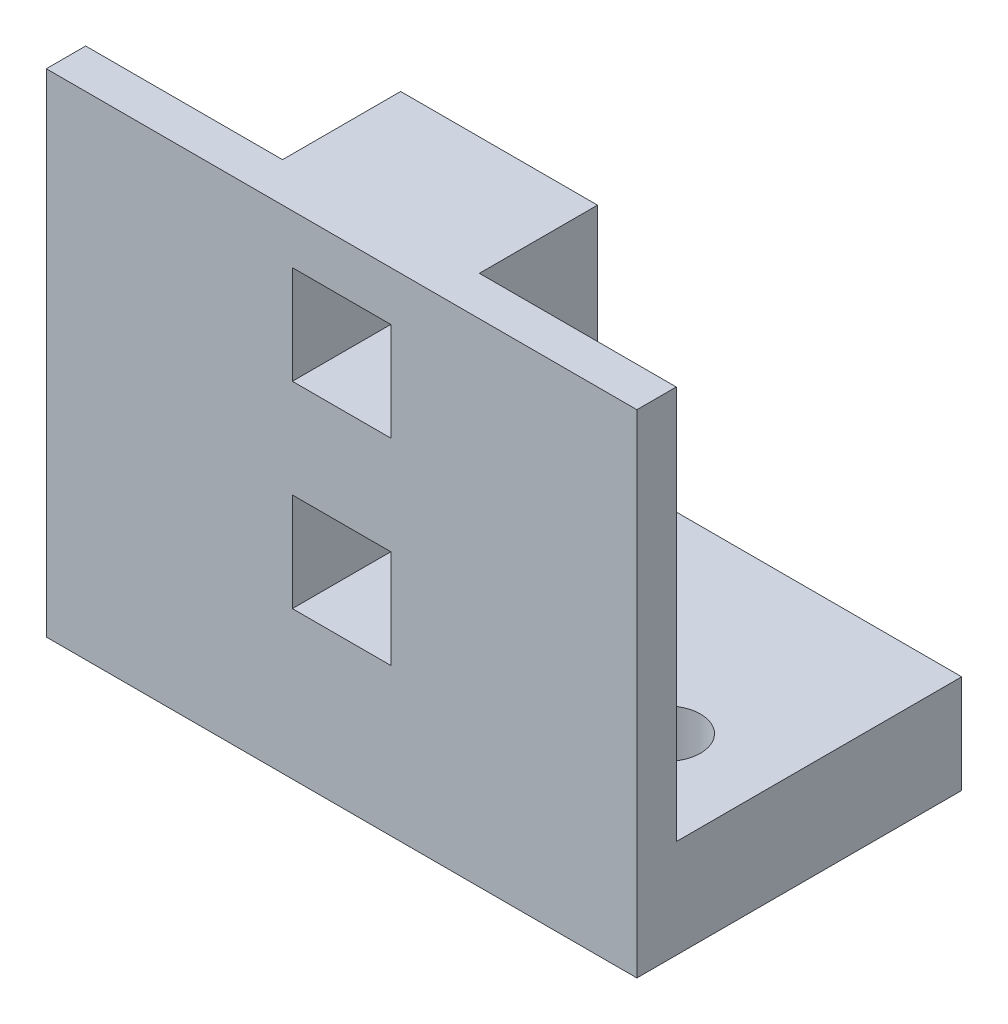
SolidWorks part; units mm, degrees
ref_plane "Front Plane" through (0, 0, 0) normal (0, 0, 1) x (1, 0, 0)
ref_plane "Top Plane" through (0, 0, 0) normal (0, 1, 0) x (1, 0, 0)
ref_plane "Right Plane" through (0, 0, 0) normal (1, 0, 0) x (0, 0, -1)
sketch "Sketch1" plane through (0, 0, 0) normal (0, 1, 0) x (1, 0, 0)
  line L1 (-15, 8.25) -> (15, 8.25)
  line L2 (-15, 8.25) -> (-15, -8.25)
  line L3 (-15, -8.25) -> (15, -8.25)
  line L4 (15, 8.25) -> (15, -8.25)
  line L5 (-15, 8.25) -> (15, -8.25) construction
  line L6 (-15, -8.25) -> (15, 8.25) construction
  circle A0 centre (-10, -1.75) radius 1.6514
  circle A1 centre (10, -1.75) radius 1.7283
  point P0 (0, 0)
  dimension "D3" = 10
  dimension "D4" = 10
  dimension "D5" = 5
  dimension "D1" = 16.5
  dimension "D2" = 30
  dimension "D6" = 5
extrude "Boss-Extrude1" add sketch "Sketch1" along normal blind 5
sketch "Sketch2" plane through (0, 0, 8.25) normal (0, 0, 1) x (1, 0, 0)
  line L1 (-15, 5) -> (15, 5)
  line L2 (-15, 5) -> (-15, 25)
  line L3 (-15, 25) -> (15, 25)
  line L4 (15, 5) -> (15, 25)
  dimension "D1" = 20
extrude "Boss-Extrude2" add sketch "Sketch2" against normal blind 2
sketch "Sketch3" plane through (0, 0, 6.25) normal (0, 0, -1) x (-1, 0, 0)
  line L0 (15, 5) -> (-15, 5) construction
  line L9 (-2.5, 7.5) -> (2.5, 7.5)
  line L10 (-2.5, 7.5) -> (-2.5, 12.5)
  line L11 (-2.5, 12.5) -> (2.5, 12.5)
  line L12 (2.5, 7.5) -> (2.5, 12.5)
  line L13 (-2.5, 17.5) -> (2.5, 17.5)
  line L14 (-2.5, 17.5) -> (-2.5, 22.5)
  line L15 (-2.5, 22.5) -> (2.5, 22.5)
  line L16 (2.5, 17.5) -> (2.5, 22.5)
  line L17 (-15, 25) -> (15, 25) construction
  line L18 (-15, 5) -> (-15, 25) construction
  line L19 (15, 25) -> (15, 5) construction
  dimension "D1" = 5
  dimension "D2" = 5
  dimension "D3" = 5
  dimension "D4" = 5
  dimension "D5" = 5
  dimension "D6" = 2.5
  dimension "D7" = 2.5
  dimension "D8" = 12.5
  dimension "D9" = 12.5
  dimension "D10" = 12.5
extrude "Cut-Extrude1" cut sketch "Sketch3" against normal through all
sketch "Sketch4" plane through (0, 0, 6.25) normal (0, 0, -1) x (-1, 0, 0)
  line L0 (-15, 25) -> (15, 25) construction
  line L1 (-5, 25) -> (5, 25)
  line L2 (-5, 25) -> (-5, 5)
  line L3 (-5, 5) -> (5, 5)
  line L4 (5, 25) -> (5, 5)
  line L5 (-15, 5) -> (15, 5) construction
  line L6 (-15, 5) -> (-15, 25) construction
  line L7 (15, 25) -> (15, 5) construction
  line L9 (-2.5, 22.5) -> (2.5, 22.5)
  line L10 (-2.5, 22.5) -> (-2.5, 17.5)
  line L11 (-2.5, 17.5) -> (2.5, 17.5)
  line L12 (2.5, 22.5) -> (2.5, 17.5)
  line L13 (-2.5, 12.5) -> (2.5, 12.5)
  line L14 (-2.5, 12.5) -> (-2.5, 7.5)
  line L15 (-2.5, 7.5) -> (2.5, 7.5)
  line L16 (2.5, 12.5) -> (2.5, 7.5)
  dimension "D1" = 10
  dimension "D2" = 10
extrude "Boss-Extrude3" add sketch "Sketch4" along normal blind 4
sketch "Sketch5" plane through (0, 0, 2.25) normal (0, 0, -1) x (-1, 0, 0)
  line L1 (-5, 25) -> (5, 25)
  line L2 (-5, 25) -> (-5, 5)
  line L3 (-5, 5) -> (5, 5)
  line L4 (5, 25) -> (5, 5)
extrude "Boss-Extrude4" add sketch "Sketch5" along normal blind 2
